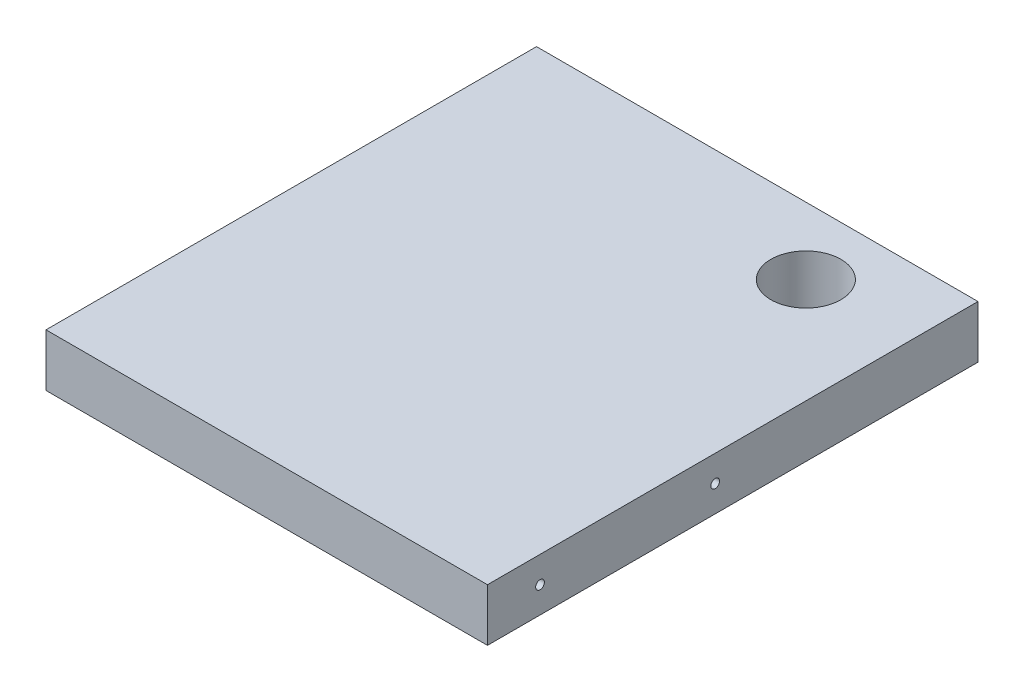
SolidWorks part; units mm, degrees
material "Beech"
ref_plane "Front Plane" through (0, 0, 0) normal (0, 0, 1) x (1, 0, 0)
ref_plane "Top Plane" through (0, 0, 0) normal (0, 1, 0) x (1, 0, 0)
ref_plane "Right Plane" through (0, 0, 0) normal (1, 0, 0) x (0, 0, -1)
sketch "Sketch1" plane through (0, 0, 0) normal (0, 0, 1) x (1, 0, 0)
  line L0 (80.01, 5194.3) -> (80.01, 5232.4) construction
  line L1 (-80.01, 5846.1044) -> (80.01, 5846.1044)
  line L2 (-80.01, 5846.1044) -> (-80.01, 5827.0544)
  line L3 (-80.01, 5827.0544) -> (80.01, 5827.0544)
  line L4 (80.01, 5846.1044) -> (80.01, 5827.0544)
  line L5 (-80.01, 5194.3) -> (-80.01, 5334) construction
  line L6 (-80.01, 5827.0544) -> (-99.06, 5827.0544) construction
  dimension "D1" = 19.05
extrude "Boss-Extrude1" add sketch "Sketch1" along normal offset from surface (177.8 mm away) 101.6 offset beyond the face yes
hole_wizard "Hole1" positions "Sketch2" profile "Sketch3" legacy
sketch "Sketch2" plane through (0, 0, -19.05) normal (0, 0, -1) x (-1, 0, 0)
  line L1 (0, 5194.3) -> (0, 5935.98) construction
  line L9 (80.01, 5836.5794) -> (-80.01, 5836.5794) construction
  point P1 (0.1622, 5756.275)
  point P4 (0, 5926.455)
  point P16 (-203.2, 5926.455)
  point P28 (-406.4, 5926.455)
  point P31 (-406.5622, 5756.275)
  point P43 (-203.3622, 5756.275)
  point P55 (-359.618, 5737.225)
  point P61 (-428.6139, 5737.225)
  point P64 (-421.2578, 5578.475)
  point P70 (-319.6578, 5578.475)
  point P82 (-116.4578, 5578.475)
  point P85 (-424.0726, 5559.425)
  point P91 (-358.1042, 5559.425)
  point P94 (-418.2303, 5400.675)
  point P100 (-316.6303, 5400.675)
  point P112 (-113.4303, 5400.675)
  point P115 (-419.5313, 5381.625)
  point P121 (-356.5904, 5381.625)
  point P124 (-415.2028, 5222.875)
  point P130 (-313.6028, 5222.875)
  point P144 (-110.4028, 5222.875)
  point P147 (-414.9901, 5203.825)
  point P153 (-355.0767, 5203.825)
  point P159 (355.0767, 5203.825)
  point P161 (414.9901, 5203.825)
  point P162 (110.4028, 5222.875)
  point P166 (313.6028, 5222.875)
  point P168 (415.2028, 5222.875)
  point P169 (356.5904, 5381.625)
  point P171 (419.5313, 5381.625)
  point P172 (113.4303, 5400.675)
  point P176 (316.6303, 5400.675)
  point P178 (418.2303, 5400.675)
  point P179 (358.1042, 5559.425)
  point P181 (424.0726, 5559.425)
  point P182 (116.4578, 5578.475)
  point P186 (319.6578, 5578.475)
  point P188 (421.2578, 5578.475)
  point P189 (428.6139, 5737.225)
  point P191 (359.618, 5737.225)
  point P195 (203.3622, 5756.275)
  point P199 (406.5622, 5756.275)
  point P200 (406.4, 5926.455)
  point P204 (203.2, 5926.455)
  point P208 (-0.1622, 5756.275)
  point P252 (0, 5836.5794)
  point P254 (-60.96, 5836.5794)
  point P256 (60.96, 5836.5794)
sketch "Sketch3" plane through (-0.1622, 5756.275, -19.05) normal (1, 0, 0) x (0, 1, 0)
  line L0 (0, 0) -> (0, 32.346)
  line L1 (0, 32.346) -> (0.9919, 31.75)
  line L2 (0.9919, 31.75) -> (0.9919, 4.7029)
  line L3 (0.9919, 4.7029) -> (5.08, 0)
  line L4 (5.08, 0) -> (0, 0)
  line L5 (0, -14.3089) -> (0, 102.4216) construction
  line L6 (0, 32.346) -> (-0.9919, 31.75) construction
  line L7 (-0.9919, 4.7029) -> (-5.08, 0) construction
  dimension "Diameter" = 1.9837
  dimension "Depth" = 31.75
  dimension "C-Sink Diameter" = 10.16
  dimension "C-Sink Angle" = 82
  dimension "Drill Angle" = 118
hole_wizard "Hole3" positions "Sketch6" profile "Sketch7" legacy
sketch "Sketch6" plane through (99.06, 0, -2683.51) normal (1, 0, 0) x (0, 0, -1)
  line L0 (-2759.71, 5836.5794) -> (-2861.31, 5836.5794) construction
  point P13 (-2842.26, 5836.5794)
  point P15 (-2778.76, 5836.5794)
sketch "Sketch7" plane through (99.06, 5836.5794, 95.25) normal (0, 1, 0) x (0, 0, -1)
  line L0 (0, 0) -> (0, 32.7039)
  line L1 (0, 32.7039) -> (1.5875, 31.75)
  line L2 (1.5875, 31.75) -> (1.5875, 4.0177)
  line L3 (1.5875, 4.0177) -> (5.08, 0)
  line L4 (5.08, 0) -> (0, 0)
  line L5 (0, -14.3089) -> (0, 102.4216) construction
  line L6 (0, 32.7039) -> (-1.5875, 31.75) construction
  line L7 (-1.5875, 4.0177) -> (-5.08, 0) construction
  dimension "Diameter" = 3.175
  dimension "Depth" = 31.75
  dimension "C-Sink Diameter" = 10.16
  dimension "C-Sink Angle" = 82
  dimension "Drill Angle" = 118
hole_wizard "Hole4" positions "Sketch8" profile "Sketch9" legacy
sketch "Sketch8" plane through (-99.06, 0, -2683.51) normal (-1, 0, 0) x (0, 0, 1)
  line L0 (2759.71, 5836.5794) -> (2861.31, 5836.5794) construction
  point P12 (2842.26, 5836.5794)
  point P14 (2778.76, 5836.5794)
sketch "Sketch9" plane through (-99.06, 5836.5794, 95.25) normal (0, 1, 0) x (0, 0, 1)
  line L0 (0, 0) -> (0, 32.7039)
  line L1 (0, 32.7039) -> (1.5875, 31.75)
  line L2 (1.5875, 31.75) -> (1.5875, 4.0177)
  line L3 (1.5875, 4.0177) -> (5.08, 0)
  line L4 (5.08, 0) -> (0, 0)
  line L5 (0, -14.3089) -> (0, 102.4216) construction
  line L6 (0, 32.7039) -> (-1.5875, 31.75) construction
  line L7 (-1.5875, 4.0177) -> (-5.08, 0) construction
  dimension "Diameter" = 3.175
  dimension "Depth" = 31.75
  dimension "C-Sink Diameter" = 10.16
  dimension "C-Sink Angle" = 82
  dimension "Drill Angle" = 118
hole_wizard "1 (1) Diameter Hole1" positions "Sketch10" profile "Sketch11" hole size "1" standard "ANSI Inch" end condition up to next
sketch "Sketch10" plane through (0, 5827.0544, 0) normal (0, -1, 0) x (-1, 0, 0)
  line L0 (80.01, 0) -> (-80.01, 0) construction
  line L1 (-80.01, -177.8) -> (-80.01, 0) construction
  point P0 (-41.91, -24.2952)
  dimension "D1" = 24.2952
  dimension "D2" = 38.1
sketch "Sketch11" plane through (41.91, 5827.0544, 24.2952) normal (1, 0, 0) x (0, 0, -1)
  line L0 (0, 0) -> (0, 19.05)
  line L1 (0, 19.05) -> (12.7, 19.05)
  line L2 (12.7, 19.05) -> (12.7, 0)
  line L5 (12.7, 0) -> (0, 0)
  line L11 (0, -6.35) -> (0, 107.95) construction
  dimension "Thru Hole Dia." = 25.4
  dimension "Thru Hole Depth" = 19.05
